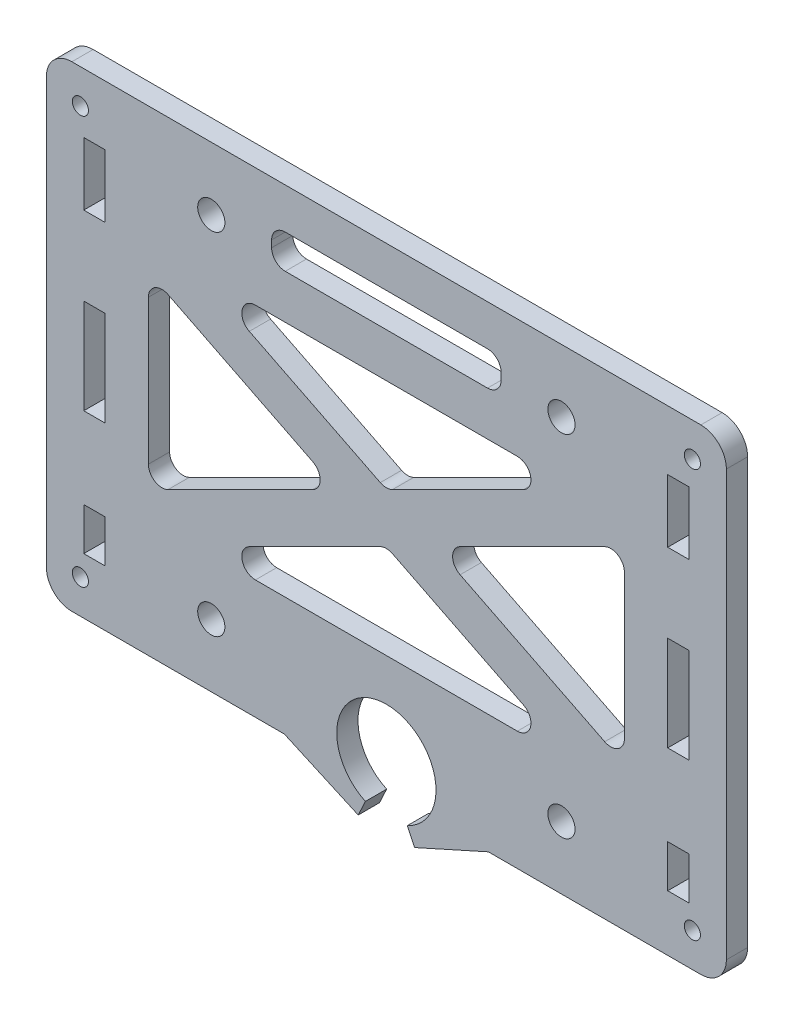
SolidWorks part; units mm, degrees
material "Delrin 2700 NC010, Low Viscosity Acetal Copolymer (SS)"
ref_plane "Front Plane" through (0, 0, 0) normal (0, 0, 1) x (1, 0, 0)
ref_plane "Top Plane" through (0, 0, 0) normal (0, 1, 0) x (1, 0, 0)
ref_plane "Right Plane" through (0, 0, 0) normal (1, 0, 0) x (0, 0, -1)
sketch "Sketch1" plane through (0, 0, 0) normal (0, 0, 1) x (1, 0, 0)
  line L0 (0, -1000) -> (0, 49000) construction
  line L1 (23.495, 17.78) -> (-23.495, 17.78)
  line L2 (25.4, 15.875) -> (25.4, -17.78)
  line L3 (25.4, -17.78) -> (-25.4, -17.78)
  line L4 (-25.4, 15.875) -> (-25.4, -17.78)
  line L5 (25.4, 17.78) -> (-25.4, -17.78) construction
  line L6 (25.4, -17.78) -> (-25.4, 17.78) construction
  line L7 (-1000, 0) -> (49000, 0) construction
  line L8 (-7.62, -17.78) -> (-2.104, -20.26)
  line L15 (-2.104, -20.26) -> (0, -15.748)
  line L16 (7.62, -17.78) -> (2.104, -20.26)
  line L17 (2.104, -20.26) -> (0, -15.748)
  line L18 (0, 0) -> (-24.2469, 20.3456) construction
  line L22 (-22.606, 8.6264) -> (-21.0185, 8.6264)
  line L23 (-22.606, 11.1664) -> (-22.606, 8.6264)
  line L24 (-21.0185, 11.1664) -> (-22.606, 11.1664)
  line L25 (-21.0185, 8.6264) -> (-21.0185, 11.1664)
  line L37 (-22.606, 8.6264) -> (-21.0185, 8.6264)
  line L38 (-22.606, 13.3254) -> (-22.606, 8.6264)
  line L39 (-21.0185, 11.1664) -> (-22.606, 11.1664) construction
  line L40 (-21.0185, 8.6264) -> (-21.0185, 13.3254)
  line L41 (-22.606, -12.4556) -> (-21.0185, -12.4556)
  line L42 (-22.606, -10.4236) -> (-22.606, -12.4556)
  line L43 (-21.0185, -10.4236) -> (-22.606, -10.4236)
  line L44 (-21.0185, -12.4556) -> (-21.0185, -10.4236)
  line L45 (-22.606, -12.4556) -> (-21.0185, -12.4556) construction
  line L46 (-22.606, -10.4236) -> (-22.606, -13.5986)
  line L47 (-21.0185, -10.4236) -> (-22.606, -10.4236)
  line L48 (-21.0185, -13.5986) -> (-21.0185, -10.4236)
  line L57 (-22.606, 1.4156) -> (-25.4, 1.4156) construction
  line L58 (22.606, 1.4156) -> (25.4, 1.4156) construction
  line L61 (-22.606, -13.5986) -> (-21.0185, -13.5986)
  line L62 (-21.0185, 13.3254) -> (-22.606, 13.3254)
  line L63 (22.606, -12.4556) -> (21.0185, -12.4556) construction
  line L64 (22.606, -13.5986) -> (21.0185, -13.5986)
  line L65 (21.0185, -13.5986) -> (21.0185, -10.4236)
  line L66 (21.0185, -10.4236) -> (22.606, -10.4236)
  line L67 (22.606, -10.4236) -> (22.606, -13.5986)
  line L68 (21.0185, 11.1664) -> (22.606, 11.1664) construction
  line L69 (21.0185, 13.3254) -> (22.606, 13.3254)
  line L70 (21.0185, 8.6264) -> (21.0185, 13.3254)
  line L71 (22.606, 13.3254) -> (22.606, 8.6264)
  line L72 (22.606, 8.6264) -> (21.0185, 8.6264)
  line L107 (22.606, 2.7432) -> (21.0185, 2.7432)
  line L108 (22.606, -4.3561) -> (21.0185, -4.3561)
  line L109 (22.606, 2.7432) -> (22.606, -4.3561)
  line L110 (21.0185, -4.3561) -> (21.0185, 2.7432)
  line L111 (-21.0185, -4.3561) -> (-21.0185, 2.7432)
  line L112 (-22.606, 2.7432) -> (-22.606, -4.3561)
  line L113 (-22.606, -4.3561) -> (-21.0185, -4.3561)
  line L114 (-22.606, 2.7432) -> (-21.0185, 2.7432)
  circle A0 centre (0, -15.748) radius 3.7084
  circle A1 centre (-22.86, 15.24) radius 0.6032
  circle A2 centre (-13.08, -13.08) radius 1.016
  circle A3 centre (22.86, 15.24) radius 0.6033
  circle A4 centre (-13.08, 13.08) radius 1.016
  circle A5 centre (13.08, 13.08) radius 1.016
  circle A6 centre (13.08, -13.08) radius 1.016
  arc A7 (23.495, -17.78) -> (25.4, -15.875) centre (23.495, -15.875) ccw
  arc A8 (-23.495, -17.78) -> (-25.4, -15.875) centre (-23.495, -15.875) cw
  arc A9 (-23.495, 17.78) -> (-25.4, 15.875) centre (-23.495, 15.875) ccw
  arc A10 (23.495, 17.78) -> (25.4, 15.875) centre (23.495, 15.875) cw
  circle A11 centre (22.86, -15.24) radius 0.6033
  circle A12 centre (-22.86, -15.24) radius 0.6032
  circle A13 centre (0, -15.748) radius 4.9784
  point P0 (0, 0)
  point P9 (0, 0)
  point P11 (0, -7.366)
  point P53 (-13.97, 0)
  dimension "D6" = 7.4168
  dimension "D7" = 1.2065
  dimension "D9" = 2.032
  dimension "D12" = 0
  dimension "D13" = 0
  dimension "D14" = 1.905
  dimension "D15" = 1.905
  dimension "D30" = 2.54
  dimension "D1" = 35.56
  dimension "D5" = 15.748
  dimension "D8" = 2.54
  dimension "D10" = 13.08
  dimension "D11" = 13.08
  dimension "D17" = 2.159
  dimension "D18" = 7.0993
  dimension "D16" = 1.143
  dimension "D19" = 40
  dimension "D20" = 8.382
  dimension "D23" = 13.97
  dimension "D24" = 1.5875
  dimension "D25" = 2.7432
  dimension "D27" = 7.62
  dimension "D28" = 25
  dimension "D29" = 2.794
  dimension "D26" = 1.27
extrude "Boss-Extrude1" add sketch "Sketch1" along normal blind 1.5875 contours A10 L1 A9 L4 L3 A0 L2 A6 A5 A4 A1 A2 A3 | L3 A13 L15 A0 | A13 L3 L8 | L3 A13 A0 | L17 A13 L3 A0 | A13 L16 L3 region at (0, 0.4974, 0) region at (5.0756, -18.4873, 0) region at (-5.0756, -18.4873, 0) region at (2.9865, -18.87, 0) region at (3.8235, -17.6582, 0) region at (-2.9865, -18.87, 0)
ref_axis "Axis1" through (0, 0, 0) along (0, 0, 1)
sketch "Sketch2" plane through (0, 0, 1.5875) normal (0, 0, 1) x (1, 0, 0)
  line L0 (0, -1000) -> (0, 49000) construction
  line L1 (-1000, 0) -> (49000, 0) construction
  line L2 (18.0067, -7.1575) -> (-14.0883, 8.89)
  line L3 (17.78, 8.89) -> (-17.78, 8.89)
  line L4 (17.78, 8.89) -> (17.78, -8.89)
  line L5 (17.78, -8.89) -> (-17.78, -8.89)
  line L6 (-17.78, 8.89) -> (-17.78, -8.89)
  line L7 (17.78, 8.89) -> (-17.78, -8.89) construction
  line L8 (17.78, -8.89) -> (-17.78, 8.89) construction
  line L9 (14.0883, 8.89) -> (-17.78, -7.0441)
  line L10 (14.0883, -8.89) -> (-17.78, 7.0441)
  line L11 (17.78, 7.0441) -> (-14.0883, -8.89)
  line L12 (18.5183, 7.4133) -> (-17.0417, -10.3667) construction
  line L13 (17.0417, 10.3667) -> (-18.5183, -7.4133) construction
  line L14 (17.0417, -10.3667) -> (-18.5183, 7.4133) construction
  line L15 (18.5183, -7.4133) -> (-17.0417, 10.3667) construction
  line L16 (23.495, 17.78) -> (-23.495, 17.78) construction
  line L17 (8.5725, 14.732) -> (-8.5725, 14.732)
  line L18 (8.5725, 14.732) -> (8.5725, 12.192)
  line L19 (8.5725, 12.192) -> (-8.5725, 12.192)
  line L20 (-8.5725, 14.732) -> (-8.5725, 12.192)
  line L21 (8.5725, 14.732) -> (-8.5725, 12.192) construction
  line L22 (8.5725, 12.192) -> (-8.5725, 14.732) construction
  point P4 (0, 0)
  point P26 (0, 13.462)
  dimension "D3" = 17.78
  dimension "D4" = 35.56
  dimension "D5" = 3.048
  dimension "D6" = 3.302
  dimension "D7" = 17.145
  dimension "D1" = 1.651
  dimension "D2" = 1.651
extrude "Speed Holes" cut sketch "Sketch2" against normal up to next contours L9 L10 L6 | L9 L3 L2 | L4 L11 L2 | L10 L11 L5 | L17 L20 L19 L18 region at (13.0839, 0, 1.5875) region at (0, 6.542, 1.5875) region at (0, -6.542, 1.5875) region at (-13.0839, 0, 1.5875) region at (0, 13.462, 1.5875)
fillet "Fillet1" radius 1.016 16 edges at (-14.0883, -8.89, 0.7937) (-17.78, -7.0441, 0.7937) (0, 1.8459, 0.7937) (14.0883, -8.89, 0.7937) (17.78, -7.0441, 0.7937) (17.78, 7.0441, 0.7937) (-3.6917, 0, 0.7937) (14.0883, 8.89, 0.7937) (3.6917, 0, 0.7937) (-14.0883, 8.89, 0.7937) (0, -1.8459, 0.7937) (-17.78, 7.0441, 0.7937) (-8.5725, 14.732, 0.7937) (-8.5725, 12.192, 0.7937) (8.5725, 14.732, 0.7937) (8.5725, 12.192, 0.7937)
